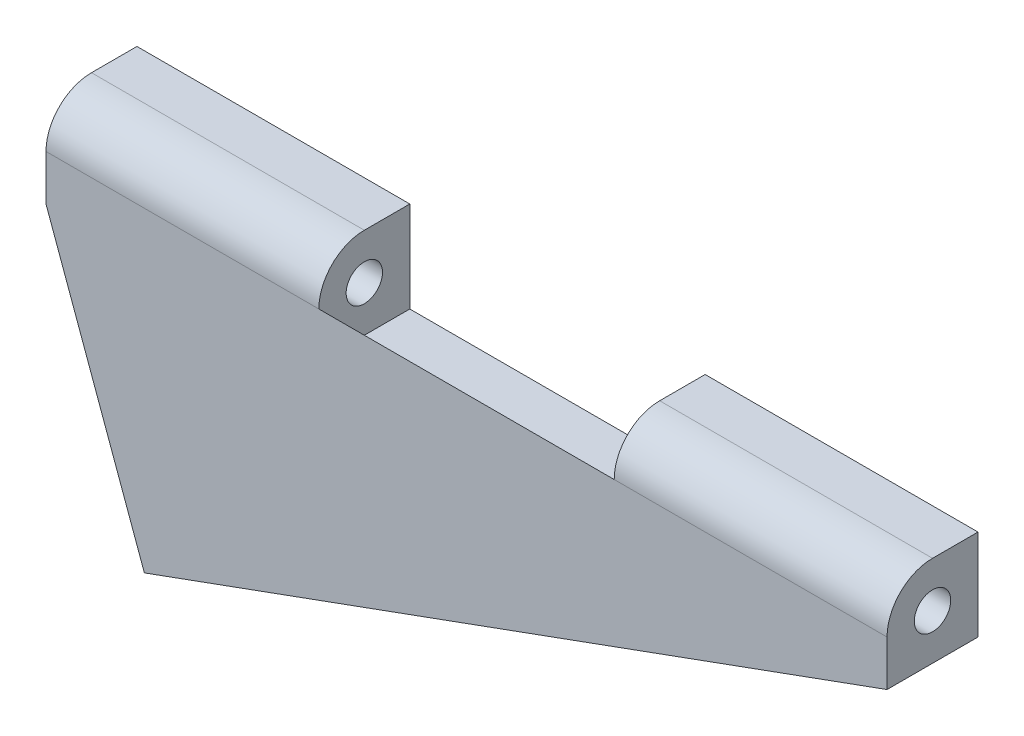
SolidWorks part; units mm, degrees
material "ABS PC"
ref_plane "Front Plane" through (0, 0, 0) normal (0, 0, 1) x (1, 0, 0)
ref_plane "Top Plane" through (0, 0, 0) normal (0, 1, 0) x (1, 0, 0)
ref_plane "Right Plane" through (0, 0, 0) normal (1, 0, 0) x (0, 0, -1)
sketch "Sketch1" plane through (0, 0, 0) normal (0, 0, 1) x (1, 0, 0)
  line L0 (-51.8514, -18.8724) -> (0, 0)
  line L1 (0, 0) -> (-58.7204, 0)
  line L2 (-58.7204, 0) -> (-51.8514, -18.8724)
  dimension "D1" = 70
  dimension "D2" = 90
  dimension "D3" = 0
  dimension "D4" = 0
  dimension "D5" = 58.7204
extrude "Boss-Extrude1" add sketch "Sketch1" along normal blind 6.35
sketch "Sketch3" plane through (0, 0, 0) normal (1, 0, 0) x (0, 0, -1)
  line L0 (-6.35, 0) -> (0, 0) construction
  line L1 (-3.175, 6.35) -> (0, 6.35)
  line L2 (0, 0) -> (0, 6.35)
  line L3 (-3.175, 0) -> (0, 0)
  line L4 (-3.175, 6.35) -> (-6.35, 6.35)
  line L5 (-6.35, 6.35) -> (-6.35, 0)
  line L6 (-6.35, 0) -> (-3.175, 0)
  circle A0 centre (-3.175, 3.175) radius 3.175
  circle A1 centre (-3.175, 3.175) radius 1.27
  point P5 (-3.175, 0)
  dimension "D1" = 6.35
  dimension "D4" = 2.54
  dimension "D2" = 3.175
  dimension "D3" = 0
  dimension "D5" = 90
extrude "Boss-Extrude3" add sketch "Sketch3" against normal up to vertex (58.7204 mm away) contours A0 A1 | A0 L3 L2 | A0 L2 L1 | A0 L5 L6 region at (0, 5.6408, 0.7092) region at (0, 5.3566, 0.9934) region at (0, 0.7092, 0.7092) region at (0, 0.7092, 5.6408) up to point (-58.7204, 0, 0)
extrude "Cut-Extrude3" cut sketch "Sketch3<7>" along direction (1, 0, 0) on the side against the normal offset from surface (20.6204 mm away) 19.05 from offset 19.05 contours A0 A1 | A0 L2 L1 | A0 L3 L2 | A0 region at (0, 5.6408, 0.7092) region at (0, 5.3566, 0.9934) region at (0, 0.7092, 0.7092) up to face at (-58.7204, 3.175, 1.905) offset against normal yes
sketch "Sketch3<7>" plane through (0, 0, 0) normal (1, 0, 0) x (0, 0, -1) same geometry as "Sketch3"
